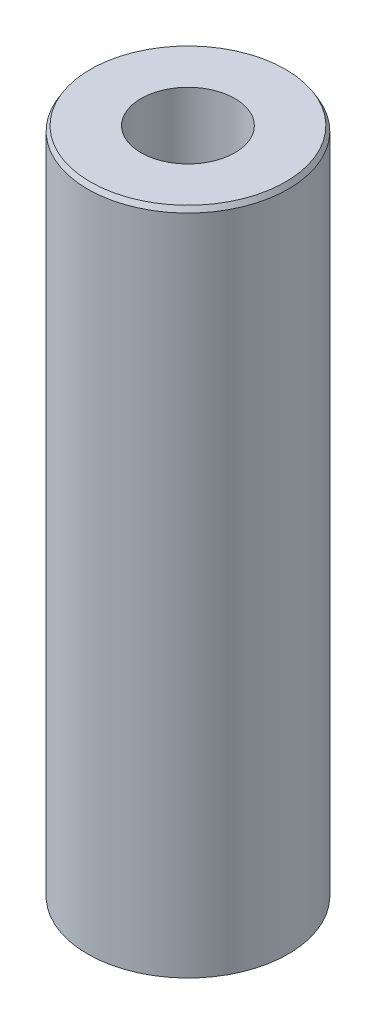
SolidWorks part; units mm, degrees
ref_plane "Front Plane" through (0, 0, 0) normal (0, 0, 1) x (1, 0, 0)
ref_plane "Top Plane" through (0, 0, 0) normal (0, 1, 0) x (1, 0, 0)
ref_plane "Right Plane" through (0, 0, 0) normal (1, 0, 0) x (0, 0, -1)
sketch "Sketch1" plane through (0, 0, 0) normal (0, 1, 0) x (1, 0, 0)
  circle A0 centre (0, 0) radius 37.5
  dimension "SHAFT_OD" = 75
extrude "Boss-Extrude1" add sketch "Sketch1" along normal blind 250.4162
sketch "Sketch2" plane through (0, 0, 0) normal (0, 1, 0) x (1, 0, 0)
  circle A0 centre (0, 0) radius 17.5621
  dimension "BORE_D" = 35.1243
extrude "Cut-Extrude1" cut sketch "Sketch2" along normal through all
chamfer "Chamfer1" distance 1.8014 angle 30 2 edges at (0, 250.4162, 37.5) (0, 0, 37.5) first distance on face at (0, 250.4162, 37.5) first distance on face at (0, 0, 17.5621)
